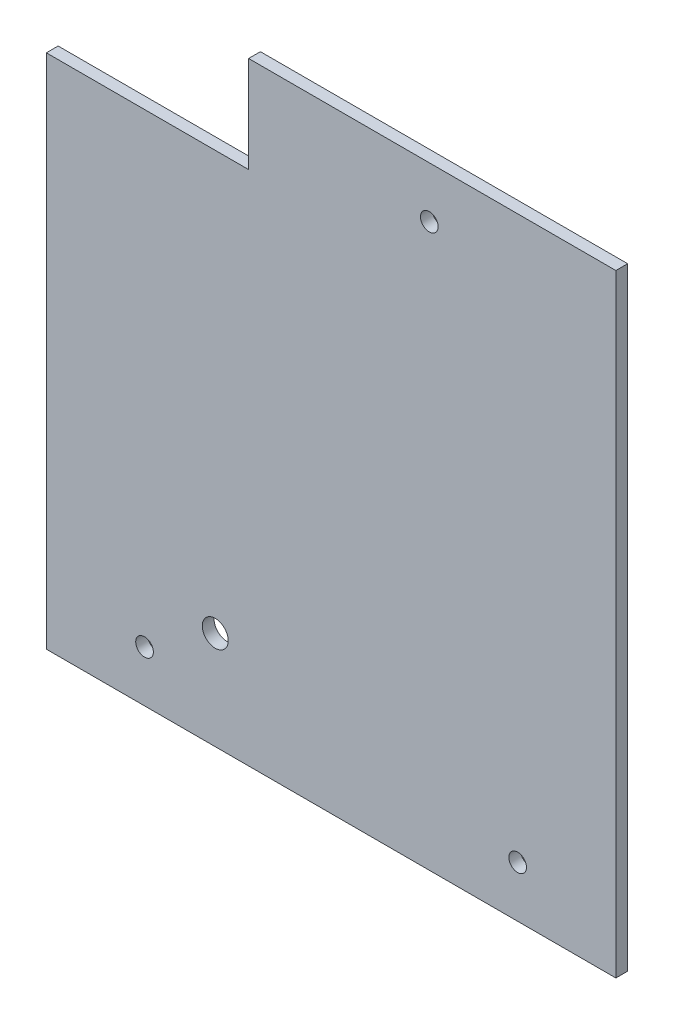
SolidWorks part; units mm, degrees
ref_plane "Ebene vorne" through (0, 0, 0) normal (0, 0, 1) x (1, 0, 0)
ref_plane "Ebene oben" through (0, 0, 0) normal (0, 1, 0) x (1, 0, 0)
ref_plane "Ebene rechts" through (0, 0, 0) normal (1, 0, 0) x (0, 0, -1)
sketch "Skizze1" plane through (0, 0, 0) normal (0, 0, 1) x (1, 0, 0)
  line L1 (72.5, -78) -> (-72.5, -78)
  line L2 (72.5, -78) -> (72.5, 78)
  line L3 (72.5, 78) -> (-72.5, 78)
  line L4 (-72.5, -78) -> (-72.5, 78)
  line L5 (72.5, -78) -> (-72.5, 78) construction
  line L6 (72.5, 78) -> (-72.5, -78) construction
  point P0 (0, 0)
  dimension "D1" = 156
  dimension "D2" = 145
extrude "Aufsatz-Linear austragen1" add sketch "Skizze1" along normal blind 3
hole_wizard "Durchgangsloch für M41" positions "Skizze2" profile "Skizze3" hole size "M4" standard "DIN"
sketch "Skizze2" plane through (0, 0, 3) normal (0, 0, 1) x (1, 0, 0)
  line L0 (-72.5, 78) -> (-72.5, -78) construction
  line L1 (72.5, 78) -> (-72.5, 78) construction
  line L3 (-72.5, -78) -> (72.5, -78) construction
  line L4 (72.5, -78) -> (72.5, 78) construction
  point P2 (25, 65)
  point P6 (-47.5, -65)
  point P25 (47.5, -65)
  dimension "D1" = 97.5
  dimension "D2" = 13
  dimension "D3" = 25
  dimension "D4" = 13
  dimension "D5" = 25
  dimension "D6" = 13
sketch "Skizze3" plane through (25, 65, 3) normal (1, 0, 0) x (0, -1, 0)
  line L0 (0, 0) -> (0, 4.3519)
  line L1 (0, 4.3519) -> (2.25, 3)
  line L2 (2.25, 3) -> (2.25, 0)
  line L5 (2.25, 0) -> (0, 0)
  line L10 (0, 4.3519) -> (-2.25, 3) construction
  line L11 (0, -6.35) -> (0, 107.95) construction
  dimension "Bohrerdurchmesser" = 4.5
  dimension "Bohrungstiefe" = 3
  dimension "Spitzenwinkel" = 118
sketch "Skizze5" plane through (0, 0, 0) normal (0, 0, -1) x (-1, 0, 0)
  line L1 (72.5, 78) -> (22.5, 78)
  line L2 (72.5, 78) -> (72.5, 55)
  line L3 (72.5, 55) -> (22.5, 55)
  line L4 (22.5, 78) -> (22.5, 55)
  dimension "D1" = 23
  dimension "D2" = 50
extrude "Schnitt-Linear austragen1" cut sketch "Skizze5" against normal through all
hole_wizard "Durchgangsloch für M61" positions "Skizze7" profile "Skizze8" hole size "M6" standard "DIN" end condition through all
sketch "Skizze7" plane through (0, 0, 3) normal (0, 0, 1) x (1, 0, 0)
  line L2 (-72.5, -78) -> (72.5, -78) construction
  line L3 (-72.5, 55) -> (-72.5, -78) construction
  circle A0 centre (-29.5, -53) radius 4
  point P6 (-29.5, -53)
  dimension "D1" = 8
  dimension "D2" = 43
  dimension "D3" = 25
sketch "Skizze8" plane through (-29.5, -53, 3) normal (1, 0, 0) x (0, -1, 0)
  line L0 (0, 0) -> (0, 3)
  line L1 (0, 3) -> (3.3, 3)
  line L2 (3.3, 3) -> (3.3, 0)
  line L5 (3.3, 0) -> (0, 0)
  line L11 (0, -6.35) -> (0, 107.95) construction
  dimension "Bohrerdurchmesser" = 6.6
  dimension "Bohrungstiefe" = 3
sketch "Skizze9" plane through (0, 0, 3) normal (0, 0, 1) x (1, 0, 0)
  line L0 (-21, 78) -> (-21, 53.5)
  line L1 (-21, 53.5) -> (-72.5, 53.5)
  line L6 (-22.5, 55) -> (-72.5, 55)
  line L7 (-72.5, 55) -> (-72.5, -78)
  line L8 (-72.5, -78) -> (72.5, -78)
  line L9 (72.5, -78) -> (72.5, 78)
  line L10 (72.5, 78) -> (-22.5, 78)
  line L11 (-22.5, 78) -> (-22.5, 55)
  line L12 (-22.5, 55) -> (-72.5, 55)
  line L13 (-72.5, 55) -> (-72.5, 53.5)
  line L16 (-21, 78) -> (-22.5, 78)
  line L17 (-22.5, 78) -> (-22.5, 55)
  dimension "D2" = 1.5
  dimension "D1" = 0
extrude "Schnitt-Linear austragen3" cut sketch "Skizze9" against normal through all
